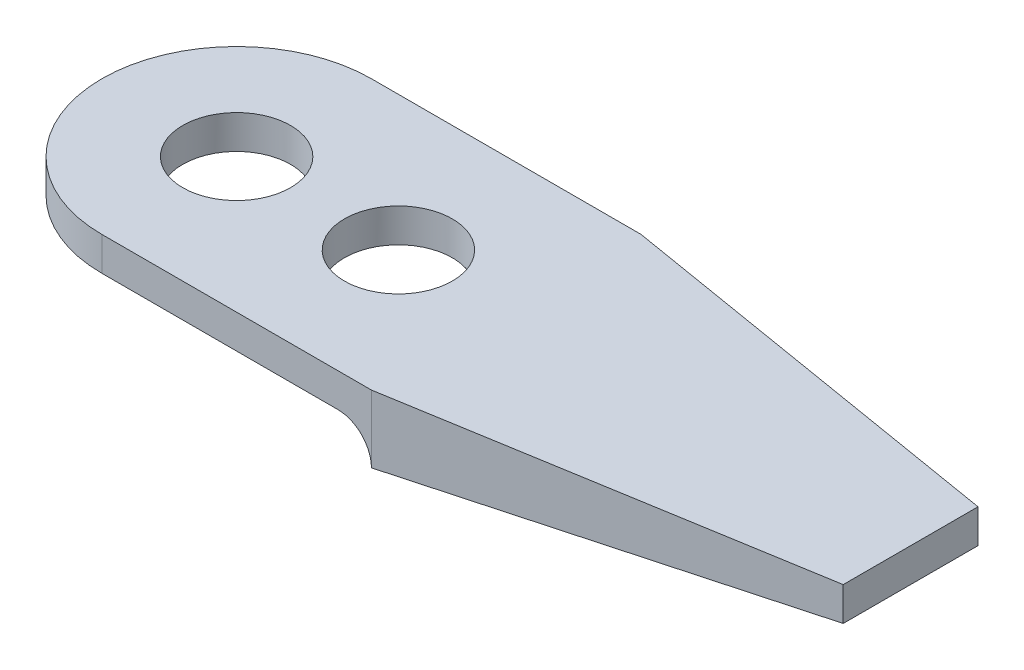
SolidWorks part; units mm, degrees
ref_plane "Front Plane" through (0, 0, 0) normal (0, 0, 1) x (1, 0, 0)
ref_plane "Top Plane" through (0, 0, 0) normal (0, 1, 0) x (1, 0, 0)
ref_plane "Right Plane" through (0, 0, 0) normal (1, 0, 0) x (0, 0, -1)
sketch "Sketch1" plane through (0, 0, 0) normal (0, 0, 1) x (1, 0, 0)
  line L0 (-19.05, 0) -> (19.05, 0)
  line L1 (55, 0) -> (-55, 0) construction
  line L2 (19.05, 0) -> (19.05, -1.5875)
  line L3 (19.05, -1.5875) -> (0, -3.175)
  line L4 (0, -55) -> (0, 55) construction
  line L5 (0, -3.175) -> (0, -1.5875)
  line L6 (0, -1.5875) -> (-19.05, -1.5875)
  line L7 (-19.05, -1.5875) -> (-19.05, 0)
  point P5 (0, 0)
  dimension "D1" = 19.05
  dimension "D2" = 19.05
extrude "Boss-Extrude1" add sketch "Sketch1" along normal mid plane 12.7
sketch "Sketch2" plane through (0, 0, 0) normal (0, 1, 0) x (1, 0, 0)
  line L0 (0, 6.35) -> (19.05, 3.175)
  line L1 (19.05, 6.35) -> (-19.05, 6.35) construction
  line L2 (19.05, -6.35) -> (19.05, 6.35) construction
  line L3 (19.05, 3.175) -> (19.05, 6.35)
  line L4 (19.05, 6.35) -> (0, 6.35)
  dimension "D1" = 3.175
extrude "Cut-Extrude1" cut sketch "Sketch2" against normal blind 12.7
mirror "Mirror1" about plane through (0, 0, 0) normal (0, 0, 1) of "Cut-Extrude1"
fillet "Fillet1" radius 6.35 2 edges at (-19.05, -0.7938, -6.35) (-19.05, -0.7938, 6.35)
fillet "Fillet2" radius 1.5875 1 edges at (0, -1.5875, 0)
sketch "Sketch3" plane through (0, 0, 0) normal (0, 1, 0) x (1, 0, 0)
  line L0 (-1.7462, 0) -> (1.7462, 0) construction
  line L1 (0, -1.7462) -> (0, 1.7462) construction
  circle A0 centre (-12.7, 0) radius 2.54
  circle A1 centre (-5.08, 0) radius 2.54
  dimension "D1" = 5.08
  dimension "D2" = 5.08
  dimension "D3" = 12.7
  dimension "D4" = 5.08
extrude "Cut-Extrude2" cut sketch "Sketch3" against normal blind 12.7
